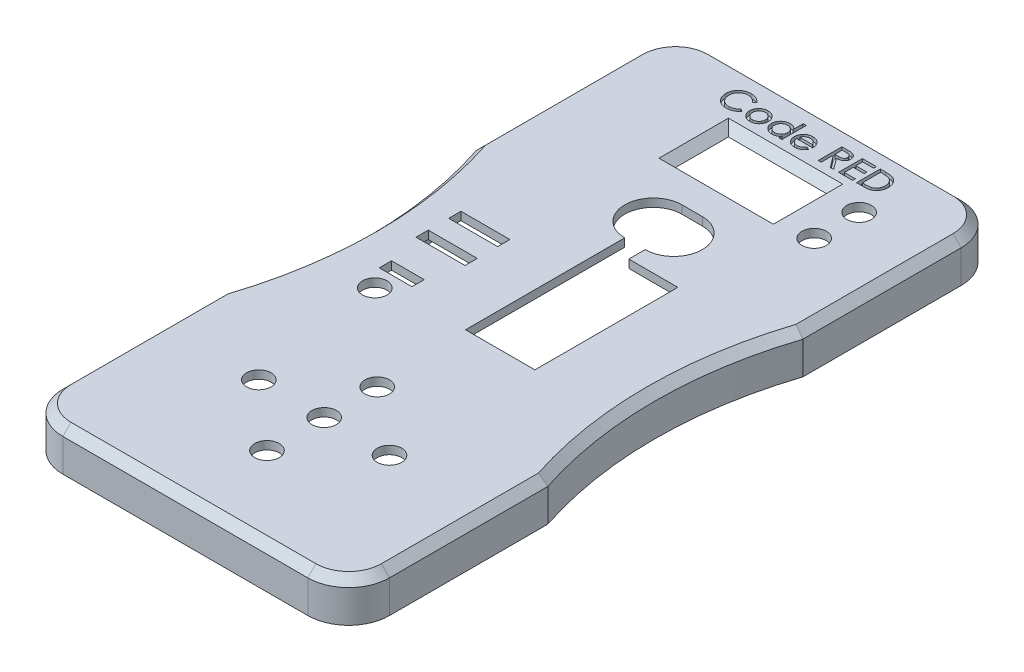
SolidWorks part; units mm, degrees
ref_plane "Front Plane" through (0, 0, 0) normal (0, 0, 1) x (1, 0, 0)
ref_plane "Top Plane" through (0, 0, 0) normal (0, 1, 0) x (1, 0, 0)
ref_plane "Right Plane" through (0, 0, 0) normal (1, 0, 0) x (0, 0, -1)
sketch "Sketch1" plane through (0, 0, 0) normal (0, 1, 0) x (1, 0, 0)
  line L1 (0, 0) -> (80, 0)
  line L2 (0, 0) -> (0, 160)
  line L3 (0, 160) -> (80, 160)
  line L4 (80, 0) -> (80, 160)
  dimension "D1" = 80
  dimension "D2" = 160
extrude "Boss-Extrude1" add sketch "Sketch1" along normal blind 10
sketch "Sketch2" plane through (0, 10, 0) normal (0, 1, 0) x (1, 0, 0)
  line L0 (40, 160) -> (40, 0) construction
  line L1 (80, 160) -> (0, 160) construction
  line L2 (0, 0) -> (80, 0) construction
  line L3 (40, 80) -> (-95, 80) construction
  line L4 (0, 160) -> (0, 0) construction
  circle A0 centre (-95, 80) radius 100
  circle A1 centre (175, 80) radius 100
  dimension "D2" = 200
  dimension "D1" = 95
extrude "Cut-Extrude1" cut sketch "Sketch2" against normal through all
fillet "Fillet1" radius 10 4 edges at (80, 5, 0) (0, 5, 0) (0, 5, -160) (80, 5, -160)
shell "Shell1" thickness 2 removed face at (40, 0, -80)
sketch "Sketch3" plane through (0, 8, 0) normal (0, -1, 0) x (1, 0, 0)
  line L0 (70, -160) -> (10, -160) construction
  line L1 (80, -111.225) -> (80, -150) construction
  line L2 (40, -158) -> (40, -2) construction
  line L3 (70, -158) -> (10, -158) construction
  line L4 (10, -2) -> (70, -2) construction
  line L5 (73, -80) -> (7, -80) construction
  circle A0 centre (70, -150) radius 4
  arc A1 (78, -48.4564) -> (78, -111.5436) centre (175, -80) ccw construction
  arc A2 (2, -111.5436) -> (2, -48.4564) centre (-95, -80) ccw construction
  circle A3 centre (10, -150) radius 4
  circle A4 centre (10, -10) radius 4
  circle A5 centre (70, -10) radius 4
  dimension "D3" = 8
  dimension "D1" = 10
  dimension "D2" = 10
extrude "Boss-Extrude2" add sketch "Sketch3" along normal through all
sketch "Sketch4" plane through (0, 0, 0) normal (0, -1, 0) x (1, 0, 0)
  line L0 (40, -158) -> (40, -2) construction
  line L1 (70, -158) -> (10, -158) construction
  line L2 (10, -2) -> (70, -2) construction
  line L3 (73, -80) -> (7, -80) construction
  circle A0 centre (70, -150) radius 2
  circle A1 centre (10, -150) radius 2
  arc A2 (78, -48.4564) -> (78, -111.5436) centre (175, -80) ccw construction
  arc A3 (2, -111.5436) -> (2, -48.4564) centre (-95, -80) ccw construction
  circle A4 centre (10, -10) radius 2
  circle A5 centre (70, -10) radius 2
  dimension "D1" = 4
extrude "Boss-Extrude3" add sketch "Sketch4" along normal blind 5
sketch "Sketch5" plane through (0, 10, 0) normal (0, 1, 0) x (1, 0, 0)
  line L0 (10, 15) -> (70, 15) construction
  line L1 (70, 15) -> (70, 125) construction
  line L2 (70, 125) -> (10, 125) construction
  line L3 (10, 125) -> (10, 15) construction
  line L4 (10, 0) -> (70, 0) construction
  line L5 (0, 48.775) -> (0, 10) construction
  line L12 (40, 15) -> (40, 47) construction
  line L13 (10, 34) -> (70, 34) construction
  circle A0 centre (40, 47) radius 3
  circle A1 centre (24, 34) radius 3
  circle A2 centre (40, 20) radius 3
  circle A3 centre (56, 34) radius 3
  circle A4 centre (40, 34) radius 3
  dimension "D7" = 6
  dimension "D8" = 6
  dimension "D9" = 6
  dimension "D10" = 6
  dimension "D11" = 6
  dimension "D1" = 15
  dimension "D2" = 110
  dimension "D3" = 10
  dimension "D4" = 60
  dimension "D5" = 32
  dimension "D6" = 19
  dimension "D12" = 14
  dimension "D13" = 14
  dimension "D14" = 5
extrude "Cut-Extrude2" cut sketch "Sketch5" against normal through all
sketch "Sketch7" plane through (0, 10, 0) normal (0, 1, 0) x (1, 0, 0)
  line L0 (10, 15) -> (70, 15) construction
  line L1 (70, 15) -> (70, 125) construction
  line L2 (70, 125) -> (10, 125) construction
  line L3 (10, 125) -> (10, 15) construction
  line L4 (10, 0) -> (70, 0) construction
  line L5 (0, 48.775) -> (0, 10) construction
  line L6 (80, 10) -> (80, 48.775) construction
  line L7 (0, 150) -> (0, 111.225) construction
  line L8 (38.69, 104.92) -> (55.69, 104.92)
  line L9 (38.69, 104.92) -> (38.69, 69.92)
  line L10 (38.69, 69.92) -> (55.69, 69.92)
  line L11 (55.69, 104.92) -> (55.69, 69.92)
  line L16 (28, 145) -> (52, 145)
  line L17 (28, 145) -> (28, 132)
  line L18 (28, 132) -> (52, 132)
  line L19 (52, 145) -> (52, 132)
  line L20 (70, 160) -> (10, 160) construction
  line L22 (13, 86.5) -> (25, 86.5)
  line L23 (13, 86.5) -> (13, 83.5)
  line L24 (13, 83.5) -> (25, 83.5)
  line L25 (25, 86.5) -> (25, 83.5)
  line L26 (13, 86.5) -> (25, 83.5) construction
  line L27 (13, 83.5) -> (25, 86.5) construction
  line L29 (13, 94.5) -> (25, 94.5)
  line L30 (13, 94.5) -> (13, 91.5)
  line L31 (13, 91.5) -> (25, 91.5)
  line L32 (25, 94.5) -> (25, 91.5)
  line L33 (13, 94.5) -> (25, 91.5) construction
  line L34 (13, 91.5) -> (25, 94.5) construction
  line L36 (15, 72.5) -> (23, 72.5)
  line L37 (15, 72.5) -> (15, 75.5)
  line L38 (15, 75.5) -> (23, 75.5)
  line L39 (23, 72.5) -> (23, 75.5)
  line L40 (15, 72.5) -> (23, 75.5) construction
  line L41 (15, 75.5) -> (23, 72.5) construction
  circle A0 centre (18.7, 67.7) radius 3
  point P24 (19, 85)
  point P33 (19, 74)
  point P36 (19, 93)
  dimension "D13" = 6
  dimension "D20" = 51
  dimension "D21" = 51
  dimension "D1" = 15
  dimension "D2" = 10
  dimension "D3" = 10
  dimension "D4" = 110
  dimension "D5" = 35
  dimension "D6" = 17
  dimension "D7" = 14.31
  dimension "D8" = 54.92
  dimension "D9" = 24
  dimension "D10" = 13
  dimension "D11" = 28
  dimension "D12" = 15
  dimension "D14" = 52.7
  dimension "D15" = 51.3
  dimension "D16" = 70
  dimension "D17" = 12
  dimension "D18" = 3
  dimension "D19" = 51
  dimension "D26" = 12
  dimension "D27" = 3
  dimension "D29" = 78
  dimension "D30" = 3
  dimension "D31" = 8
  dimension "D32" = 59
extrude "Cut-Extrude3" cut sketch "Sketch7" against normal through all
chamfer "Chamfer1" distance 2 angle 45 4 edges at (52, 10, -138.5) (40, 10, -132) (28, 10, -138.5) (40, 10, -145)
chamfer "Chamfer2" distance 2 angle 45 12 edges at (5, 10, -80) (0, 10, -29.3875) (2.9289, 10, -2.9289) (40, 10, 0) (77.0711, 10, -2.9289) (80, 10, -29.3875) (75, 10, -80) (80, 10, -130.6125) (77.0711, 10, -157.0711) (0, 10, -130.6125) (2.9289, 10, -157.0711) (40, 10, -160)
sketch "Sketch13" plane through (0, 10, 0) normal (0, 1, 0) x (1, 0, 0)
  line L0 (20, 149) -> (56, 149) construction
  line L1 (10, 160) -> (70, 160) construction
  line L2 (0, 111.225) -> (0, 150) construction
  text T0 "Code RED" font "Century Gothic" height in points 22
  dimension "D1" = 36
  dimension "D2" = 11
  dimension "D3" = 20
extrude "Cut-Extrude7" cut sketch "Sketch13" against normal blind 1
sketch "Sketch14" plane through (0, 10, 0) normal (0, 1, 0) x (1, 0, 0)
  line L0 (43.69, 122.92) -> (43.69, 104.92) construction
  line L1 (80, 150) -> (80, 111.225) construction
  line L2 (55.69, 104.92) -> (38.69, 104.92) construction
  line L3 (43.69, 104.92) -> (38.69, 104.92) construction
  line L4 (38.69, 104.92) -> (38.69, 122.92) construction
  line L5 (38.69, 122.92) -> (43.69, 122.92) construction
  line L6 (38.69, 108.92) -> (43.69, 108.92) construction
  line L7 (38.69, 122.92) -> (43.69, 122.92)
  line L8 (38.69, 108.92) -> (38.69, 104.92)
  line L9 (38.69, 104.92) -> (43.69, 104.92)
  line L10 (43.69, 104.92) -> (43.69, 108.92)
  line L11 (10, 160) -> (70, 160) construction
  arc A0 (38.69, 108.92) -> (38.69, 122.92) centre (38.69, 115.92) cw
  arc A1 (43.69, 122.92) -> (43.69, 108.92) centre (43.69, 115.92) cw
  circle A2 centre (62, 143) radius 3
  circle A3 centre (62, 132) radius 3
  dimension "D4" = 6
  dimension "D5" = 6
  dimension "D6" = 17
  dimension "D1" = 5
  dimension "D2" = 18
  dimension "D3" = 4
  dimension "D7" = 28
  dimension "D8" = 18
  dimension "D9" = 18
extrude "Cut-Extrude8" cut sketch "Sketch14" against normal through all
sketch "Sketch15" plane through (0, 0, 0) normal (-1, 0, 0) x (0, 0, 1)
  line L0 (-150, 0) -> (-111.225, 0) construction
  line L1 (-142, 0) -> (-130, 0)
  line L2 (-142, 0) -> (-142, 8)
  line L3 (-142, 8) -> (-130, 8)
  line L4 (-130, 0) -> (-130, 8)
  line L5 (-111.225, 8) -> (-150, 8) construction
  line L6 (-160, 0) -> (-160, 8) construction
  dimension "D1" = 30
  dimension "D2" = 12
extrude "Cut-Extrude9" cut sketch "Sketch15" against normal up to next
